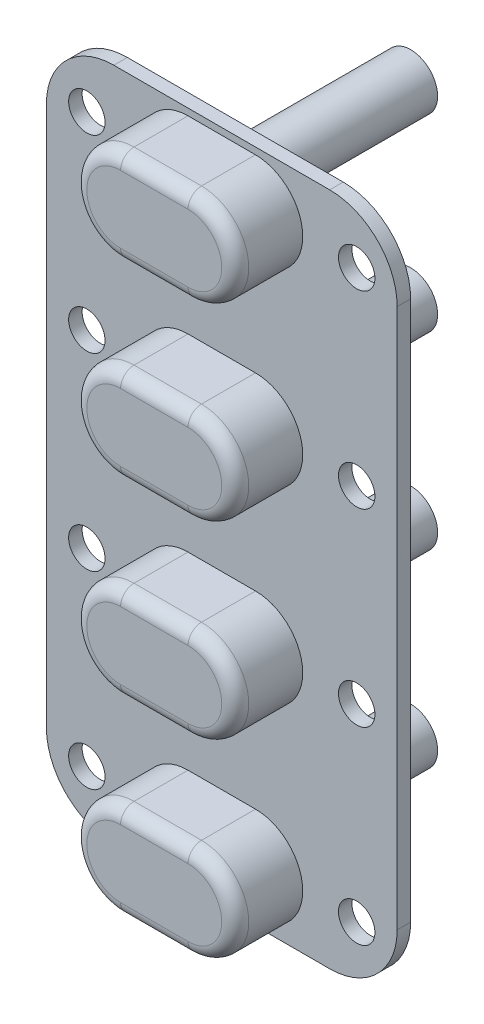
SolidWorks part; units mm, degrees
ref_plane "Front Plane" through (0, 0, 0) normal (0, 0, 1) x (1, 0, 0)
ref_plane "Top Plane" through (0, 0, 0) normal (0, 1, 0) x (1, 0, 0)
ref_plane "Right Plane" through (0, 0, 0) normal (1, 0, 0) x (0, 0, -1)
sketch "Sketch1" plane through (0, 0, 0) normal (0, 0, 1) x (1, 0, 0)
  line L1 (13, 25) -> (-13, 25)
  line L2 (13, 25) -> (13, -25)
  line L3 (13, -25) -> (-13, -25)
  line L4 (-13, 25) -> (-13, -25)
  line L5 (13, 25) -> (-13, -25) construction
  line L6 (13, -25) -> (-13, 25) construction
  circle A1 centre (10, -21) radius 1.35
  circle A9 centre (10, -7) radius 1.35
  circle A10 centre (10, 7) radius 1.35
  circle A11 centre (10, 21) radius 1.35
  circle A12 centre (-10, -7) radius 1.35
  circle A13 centre (-10, 7) radius 1.35
  circle A14 centre (-10, 21) radius 1.35
  circle A15 centre (-10, -21) radius 1.35
  point P0 (0, 0)
  dimension "D5" = 2.7
  dimension "D1" = 26
  dimension "D2" = 50
  dimension "D3" = 10
  dimension "D4" = 21
  dimension "D8" = 14
  dimension "D9" = 20
  dimension "D6" = 4
  dimension "D7" = 2
extrude "Boss-Extrude1" add sketch "Sketch1" along normal blind 1
sketch "Sketch2" plane through (0, 0, 1) normal (0, 0, 1) x (1, 0, 0)
  line L0 (-2.5, 21) -> (2.5, 21) construction
  line L1 (-2.5, 24.5) -> (2.5, 24.5)
  line L2 (-2.5, 17.5) -> (2.5, 17.5)
  line L3 (-2.5, 3.5) -> (2.5, 3.5)
  line L4 (-2.5, 10.5) -> (2.5, 10.5)
  line L5 (-2.5, 7) -> (2.5, 7) construction
  line L6 (-2.5, -10.5) -> (2.5, -10.5)
  line L7 (-2.5, -3.5) -> (2.5, -3.5)
  line L8 (-2.5, -7) -> (2.5, -7) construction
  line L9 (-2.5, -24.5) -> (2.5, -24.5)
  line L10 (-2.5, -17.5) -> (2.5, -17.5)
  line L11 (-2.5, -21) -> (2.5, -21) construction
  arc A0 (-2.5, 24.5) -> (-2.5, 17.5) centre (-2.5, 21) ccw
  arc A1 (2.5, 17.5) -> (2.5, 24.5) centre (2.5, 21) ccw
  arc A2 (-2.5, 10.5) -> (-2.5, 3.5) centre (-2.5, 7) ccw
  arc A3 (2.5, 3.5) -> (2.5, 10.5) centre (2.5, 7) ccw
  arc A4 (-2.5, -3.5) -> (-2.5, -10.5) centre (-2.5, -7) ccw
  arc A5 (2.5, -10.5) -> (2.5, -3.5) centre (2.5, -7) ccw
  arc A6 (-2.5, -17.5) -> (-2.5, -24.5) centre (-2.5, -21) ccw
  arc A7 (2.5, -24.5) -> (2.5, -17.5) centre (2.5, -21) ccw
  point P2 (0, 21)
  point P10 (0, 7)
  point P18 (0, -7)
  point P25 (0, -21)
  dimension "D2" = 3.5
  dimension "D1" = 5
  dimension "D3" = 21
  dimension "D5" = 14
  dimension "D4" = 4
extrude "Boss-Extrude2" add sketch "Sketch2" along normal blind 5
fillet "Fillet1" radius 1 16 edges at (0, -17.5, 6) (6, -21, 6) (0, -24.5, 6) (-6, -21, 6) (0, -3.5, 6) (6, -7, 6) (0, -10.5, 6) (-6, -7, 6) (0, 10.5, 6) (6, 7, 6) (0, 3.5, 6) (-6, 7, 6) (0, 24.5, 6) (6, 21, 6) (0, 17.5, 6) (-6, 21, 6)
fillet "Fillet2" radius 5 4 edges at (13, 25, 0.5) (-13, 25, 0.5) (13, -25, 0.5) (-13, -25, 0.5)
sketch "Sketch3" plane through (0, 0, 0) normal (0, 0, -1) x (-1, 0, 0)
  line L0 (10, 21) -> (-10, 21) construction
  line L1 (-10, 7) -> (10, 7) construction
  line L2 (10, -7) -> (-10, -7) construction
  line L3 (-10, -21) -> (10, -21) construction
  circle A0 centre (0, 21) radius 2
  circle A1 centre (0, 7) radius 2
  circle A2 centre (0, -7) radius 2
  circle A3 centre (0, -21) radius 2
  dimension "D1" = 4
extrude "Boss-Extrude3" add sketch "Sketch3" along normal blind 13
fillet "Fillet3" radius 2 4 edges at (-2, -21, 0) (-2, -7, 0) (-2, 7, 0) (-2, 21, 0)
